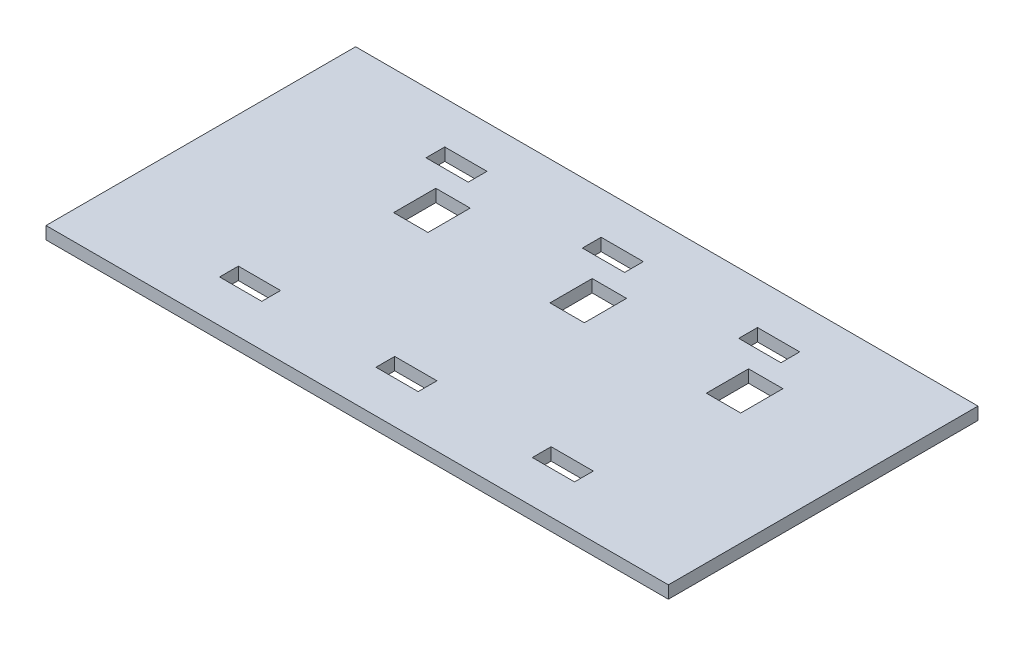
SolidWorks part; units mm, degrees
material "POLYURETHANE (11671)"
ref_plane "Front Plane" through (0, 0, 0) normal (0, 0, 1) x (1, 0, 0)
ref_plane "Top Plane" through (0, 0, 0) normal (0, 1, 0) x (1, 0, 0)
ref_plane "Right Plane" through (0, 0, 0) normal (1, 0, 0) x (0, 0, -1)
sketch "Sketch1" plane through (0, 0, 0) normal (0, 1, 0) x (1, 0, 0)
  line L1 (-50.546, -25.146) -> (50.546, -25.146)
  line L2 (-50.546, -25.146) -> (-50.546, 25.146)
  line L3 (-50.546, 25.146) -> (50.546, 25.146)
  line L4 (50.546, -25.146) -> (50.546, 25.146)
  line L5 (0, 25.146) -> (0, -25.146) construction
  line L6 (-50.546, 0) -> (50.546, 0) construction
  point P0 (0, 0)
  dimension "D1" = 50.292
  dimension "D2" = 101.092
extrude "Boss-Extrude1" add sketch "Sketch1" along normal blind 2.032
sketch "Sketch2" plane through (0, 2.032, 0) normal (0, 1, 0) x (1, 0, 0)
  line L0 (1.27, 4.8935) -> (6.858, 4.8935)
  line L1 (1.27, 4.8935) -> (1.27, 11.7515)
  line L2 (6.858, 4.8935) -> (6.858, 11.7515)
  line L3 (1.27, 11.7515) -> (6.858, 11.7515)
  circle A0 centre (4.064, 0) radius 5.635 construction
  dimension "D1" = 11.27
  dimension "D2" = 4.064
  dimension "D3" = 5.588
  dimension "D4" = 6.858
extrude "Wire Hole" cut sketch "Sketch2" against normal through all contours L3 L1 L0 L2 region at (4.064, 2.032, -8.3225)
sketch "Sketch3" plane through (0, 2.032, 0) normal (0, 1, 0) x (1, 0, 0)
  line L0 (-3.81, 15.24) -> (3.048, 15.24)
  line L1 (-3.81, 15.24) -> (-3.81, 18.288)
  line L2 (3.048, 15.24) -> (3.048, 18.288)
  line L3 (-3.81, 18.288) -> (3.048, 18.288)
  line L4 (-55, 0) -> (55, 0) construction
  dimension "D1" = 3.048
  dimension "D2" = 6.858
  dimension "D3" = 3.048
  dimension "D4" = 15.24
extrude "Cut-Extrude2" cut sketch "Sketch3" against normal through all
mirror "Mirror1" about plane through (0, 0, 0) normal (0, 0, 1) of "Cut-Extrude2"
pattern_linear "LPattern1" count 2 spacing 25.4 along (-1, 0, 0) count 2 spacing 25.4 along (1, 0, 0) of "Wire Hole", "Cut-Extrude2", "Mirror1"
equation "\"Arrow Height\"= 1in"
equation "\"Button Height\"= 2in"
equation "\"Button Width\"= 4in"
equation "\"Haptic Diameter\"= 10mm"
equation "\"Haptic Thickness\"= 2.7mm"
equation "\"D1@Sketch1\"=\"Button Height\"-\"Tolerance\""
equation "\"D2@Sketch1\"=\"Button Width\"-\"Tolerance\""
equation "\"Arrow Spacing\"= 1in"
equation "\"Arrow Width\"= 0.75in"
equation "\"Haptic Wire Angle\"= 63.43"
equation "\"Haptic Wire Width\" = .2in"
equation "\"Hatic Wire Height\"= .25in"
equation "\"D1@Sketch2\"=\"Haptic Diameter\"+.05"
equation "\"D3@Sketch2\"=\"Haptic Wire Width\"+.02"
equation "\"D4@Sketch2\"=\"Hatic Wire Height\"+.02"
equation "\"Tolerance\"= .02in"
